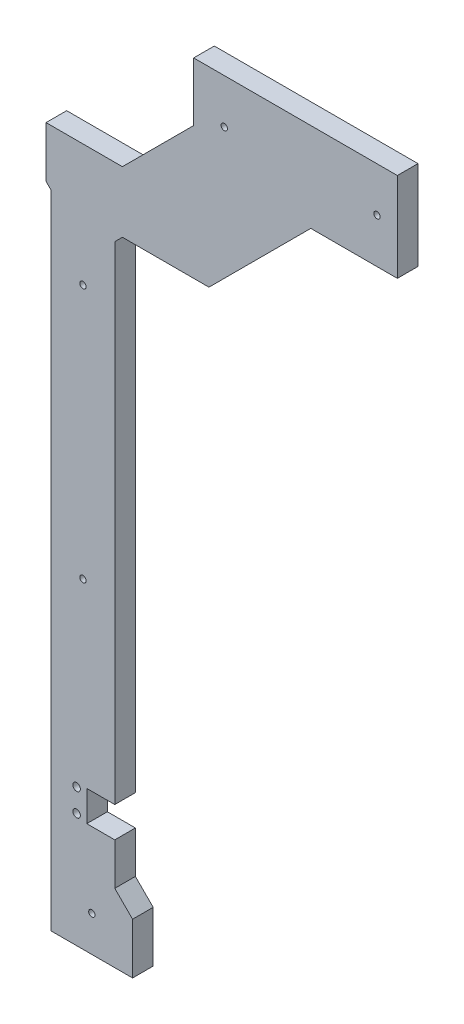
SolidWorks part; units mm, degrees
ref_plane "Plan de face" through (0, 0, 0) normal (0, 0, 1) x (1, 0, 0)
ref_plane "Plan de dessus" through (0, 0, 0) normal (0, 1, 0) x (1, 0, 0)
ref_plane "Plan de droite" through (0, 0, 0) normal (1, 0, 0) x (0, 0, -1)
sketch "Esquisse1" plane through (0, 0, 0) normal (0, 0, 1) x (1, 0, 0)
  line L1 (0, 0) -> (32, 0)
  line L2 (0, 0) -> (0, 274)
  line L3 (0, 274) -> (32, 274)
  line L4 (32, 0) -> (32, 274)
  dimension "D1" = 32
  dimension "D2" = 274
extrude "Boss.-Extru.1" add sketch "Esquisse1" along normal blind 8.1
sketch "Esquisse2" plane through (0, 0, 0) normal (0, -1, 0) x (-1, 0, 0)
  line L0 (0, -4.05) -> (-32, -4.05) construction
  line L1 (0, -8.1) -> (0, 0) construction
  line L2 (-32, -8.1) -> (-32, 0) construction
  line L3 (-16, -4.05) -> (-16, -8.1) construction
  line L4 (0, -8.1) -> (-32, -8.1) construction
  circle A0 centre (-26, -4.05) radius 1.65
  circle A1 centre (-6, -4.05) radius 1.65
  dimension "D1" = 3.3
  dimension "D2" = 20
extrude "Enlèv. mat.-Extru.1" cut sketch "Esquisse2" against normal blind 10
sketch "Esquisse3" plane through (0, 0, 8.1) normal (0, 0, 1) x (1, 0, 0)
  line L0 (32, 20) -> (25, 27)
  line L2 (32, 0) -> (32, 274) construction
  line L3 (25, 27) -> (25, 247)
  line L4 (25, 247) -> (32, 254)
  line L5 (32, 254) -> (32, 20)
  line L6 (0, 274) -> (0, 0) construction
  line L7 (0, 0) -> (32, 0) construction
  line L8 (32, 274) -> (0, 274) construction
  dimension "D1" = 45
  dimension "D2" = 25
  dimension "D3" = 20
  dimension "D4" = 20
  dimension "D5" = 45
extrude "Enlèv. mat.-Extru.2" cut sketch "Esquisse3" against normal through all
sketch "Esquisse4" plane through (0, 0, 8.1) normal (0, 0, 1) x (1, 0, 0)
  line L0 (0, 274) -> (-2, 274)
  line L1 (-2, 274) -> (-2, 254)
  line L2 (-2, 254) -> (0, 252)
  line L3 (0, 274) -> (0, 0) construction
  line L4 (0, 252) -> (0, 274)
  dimension "D1" = 20
  dimension "D2" = 45
  dimension "D3" = 2
extrude "Boss.-Extru.2" add sketch "Esquisse4" against normal up to vertex (8.1 mm away) up to point (0, 274, 0)
sketch "Esquisse5" plane through (0, 0, 8.1) normal (0, 0, 1) x (1, 0, 0)
  line L0 (32, 274) -> (-2, 274) construction
  line L1 (28, 274) -> (32, 274)
  line L2 (28, 274) -> (28, 244)
  line L3 (28, 244) -> (32, 244)
  line L4 (32, 274) -> (32, 244)
  line L5 (32, 254) -> (32, 274) construction
  dimension "D1" = 4
  dimension "D2" = 30
extrude "Enlèv. mat.-Extru.3" cut sketch "Esquisse5" against normal through all
sketch "Esquisse6" plane through (0, 0, 8.1) normal (0, 0, 1) x (1, 0, 0)
  line L0 (10, 45) -> (10, 54) construction
  line L1 (0, 0) -> (32, 0) construction
  line L2 (16, 0) -> (16, 14) construction
  line L3 (0, 126) -> (25, 126) construction
  line L4 (0, 252) -> (0, 0) construction
  line L5 (25, 247) -> (25, 27) construction
  line L6 (12.5, 126) -> (12.5, 226) construction
  line L7 (12.5, 226) -> (0, 226) construction
  circle A0 centre (10, 45) radius 1.5
  circle A1 centre (10, 54) radius 1.5
  circle A2 centre (16, 14) radius 1.25
  circle A3 centre (12.5, 126) radius 1.25
  circle A4 centre (12.5, 226) radius 1.25
  dimension "D4" = 3
  dimension "D5" = 2.5
  dimension "D1" = 9
  dimension "D2" = 45
  dimension "D3" = 10
  dimension "D6" = 14
  dimension "D7" = 100
extrude "Enlèv. mat.-Extru.4" cut sketch "Esquisse6" against normal through all
sketch "Esquisse7" plane through (0, 0, 8.1) normal (0, 0, 1) x (1, 0, 0)
  line L0 (28, 250) -> (136, 250)
  line L1 (136, 250) -> (136, 325)
  line L2 (136, 325) -> (79, 325)
  line L3 (79, 325) -> (28, 274)
  line L4 (28, 250) -> (28, 274)
  dimension "D1" = 135
  dimension "D2" = 108
  dimension "D3" = 75
extrude "Boss.-Extru.3" add sketch "Esquisse7" against normal up to vertex (8.1 mm away) up to point (-2, 274, 0)
sketch "Esquisse8" plane through (0, 0, 8.1) normal (0, 0, 1) x (1, 0, 0)
  line L0 (62, 250) -> (102, 290)
  line L1 (28, 250) -> (136, 250) construction
  line L2 (102, 290) -> (136, 290)
  line L3 (136, 250) -> (136, 325) construction
  line L4 (136, 290) -> (136, 250)
  line L5 (136, 250) -> (62, 250)
  dimension "D1" = 45
  dimension "D2" = 40
  dimension "D3" = 74
extrude "Enlèv. mat.-Extru.5" cut sketch "Esquisse8" against normal through all
sketch "Esquisse9" plane through (0, 0, 8.1) normal (0, 0, 1) x (1, 0, 0)
  line L0 (79, 325) -> (56, 325)
  line L1 (56, 325) -> (56, 302)
  line L3 (56, 302) -> (79, 325)
  line L4 (79, 325) -> (28, 274) construction
  line L6 (136, 290) -> (136, 325) construction
  dimension "D1" = 80
extrude "Boss.-Extru.4" add sketch "Esquisse9" against normal up to vertex (8.1 mm away) up to point (136, 325, 0)
sketch "Esquisse10" plane through (0, 0, 8.1) normal (0, 0, 1) x (1, 0, 0)
  line L0 (136, 307.5) -> (56, 307.5) construction
  line L1 (136, 290) -> (136, 325) construction
  line L2 (56, 325) -> (56, 302) construction
  line L3 (96, 307.5) -> (96, 325) construction
  line L4 (136, 325) -> (56, 325) construction
  circle A0 centre (128, 307.5) radius 1.25
  circle A1 centre (68, 307.5) radius 1.25
  dimension "D1" = 2.5
  dimension "D2" = 60
  dimension "D3" = 8
extrude "Enlèv. mat.-Extru.6" cut sketch "Esquisse10" against normal through all
sketch "Esquisse11" plane through (0, 0, 8.1) normal (0, 0, 1) x (1, 0, 0)
  line L0 (10, 46.5) -> (10, 52.5) construction
  line L1 (10, 49.5) -> (25, 49.5) construction
  line L2 (25, 247) -> (25, 27) construction
  line L3 (25, 55.5) -> (14, 55.5)
  line L4 (14, 55.5) -> (14, 43.5)
  line L5 (25, 43.5) -> (25, 55.5)
  line L6 (25, 43.5) -> (14, 43.5)
  circle A0 centre (10, 45) radius 1.5 construction
  circle A1 centre (10, 54) radius 1.5 construction
  point P14 (14, 49.5)
  dimension "D1" = 12
  dimension "D2" = 11
extrude "Enlèv. mat.-Extru.7" cut sketch "Esquisse11" against normal through all
